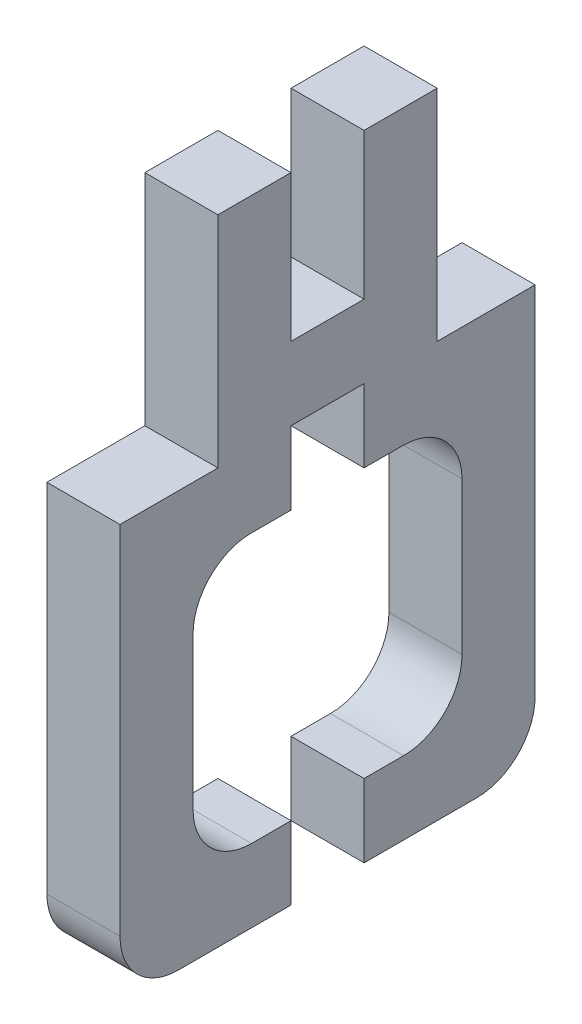
SolidWorks part; units mm, degrees
material "Pine"
ref_plane "Front Plane" through (0, 0, 0) normal (0, 0, 1) x (1, 0, 0)
ref_plane "Top Plane" through (0, 0, 0) normal (0, 1, 0) x (1, 0, 0)
ref_plane "Right Plane" through (0, 0, 0) normal (1, 0, 0) x (0, 0, -1)
sketch "Sketch2" plane through (0, 0, 0) normal (1, 0, 0) x (0, 0, -1)
  line L2 (14.859, 55.118) -> (14.859, 42.418)
  line L3 (14.859, 42.418) -> (21.209, 42.418)
  line L4 (21.209, 42.418) -> (21.209, 55.118)
  line L5 (21.209, 55.118) -> (27.559, 55.118)
  line L7 (30.988, 0) -> (5.08, 0)
  line L9 (11.43, 6.35) -> (24.638, 6.35)
  line L10 (6.35, 11.43) -> (6.35, 24.638)
  line L12 (29.718, 11.43) -> (29.718, 24.638)
  line L16 (27.559, 55.118) -> (27.559, 36.068)
  line L17 (27.559, 36.068) -> (36.068, 36.068)
  line L18 (36.068, 36.068) -> (36.068, 5.08)
  line L20 (8.509, 36.068) -> (0, 36.068)
  line L21 (0, 36.068) -> (0, 5.08)
  line L22 (14.859, 55.118) -> (8.509, 55.118)
  line L23 (8.509, 55.118) -> (8.509, 36.068)
  line L24 (24.638, 29.718) -> (21.209, 29.718)
  line L25 (21.209, 29.718) -> (21.209, 36.068)
  line L26 (21.209, 36.068) -> (14.859, 36.068)
  line L27 (14.859, 36.068) -> (14.859, 29.718)
  line L28 (14.859, 29.718) -> (11.43, 29.718)
  line L30 (14.859, 6.35) -> (21.209, 6.35)
  line L31 (14.859, 6.35) -> (14.859, 0)
  line L32 (14.859, 0) -> (21.209, 0)
  line L33 (21.209, 6.35) -> (21.209, 0)
  arc A0 (11.43, 6.35) -> (6.35, 11.43) centre (11.43, 11.43) cw
  arc A1 (24.638, 6.35) -> (29.718, 11.43) centre (24.638, 11.43) ccw
  arc A2 (24.638, 29.718) -> (29.718, 24.638) centre (24.638, 24.638) cw
  arc A3 (6.35, 24.638) -> (11.43, 29.718) centre (11.43, 24.638) cw
  arc A4 (36.068, 5.08) -> (30.988, 0) centre (30.988, 5.08) cw
  arc A5 (0, 5.08) -> (5.08, 0) centre (5.08, 5.08) ccw
  point P13 (18.034, 42.418)
  point P16 (18.034, 0)
  point P26 (18.034, 0)
  point P30 (6.35, 6.35)
  point P35 (29.718, 29.718)
  point P38 (6.35, 29.718)
  point P43 (0, 0)
  dimension "D15" = 5.08
  dimension "D16" = 5.08
  dimension "D1" = 6.35
  dimension "D2" = 23.368
  dimension "D3" = 23.368
  dimension "D4" = 6.35
  dimension "D5" = 6.35
  dimension "D6" = 6.35
  dimension "D9" = 6.35
  dimension "D10" = 6.35
  dimension "D7" = 6.35
  dimension "D8" = 6.35
  dimension "D11" = 25.4
  dimension "D12" = 6.35
  dimension "D13" = 6.35
  dimension "D14" = 6.35
extrude "Boss-Extrude1" add sketch "Sketch2" along normal blind 6.35 contours L9 L33 L7 L18 L17 L16 L5 L4 L3 L2 L22 L23 L20 L21 L31 L10 L28 L27 L26 L25 L24 L12 region at (0, 48.768, -14.2003)
equation "\"D2@Sketch2\"=\"D3@Sketch2\""
